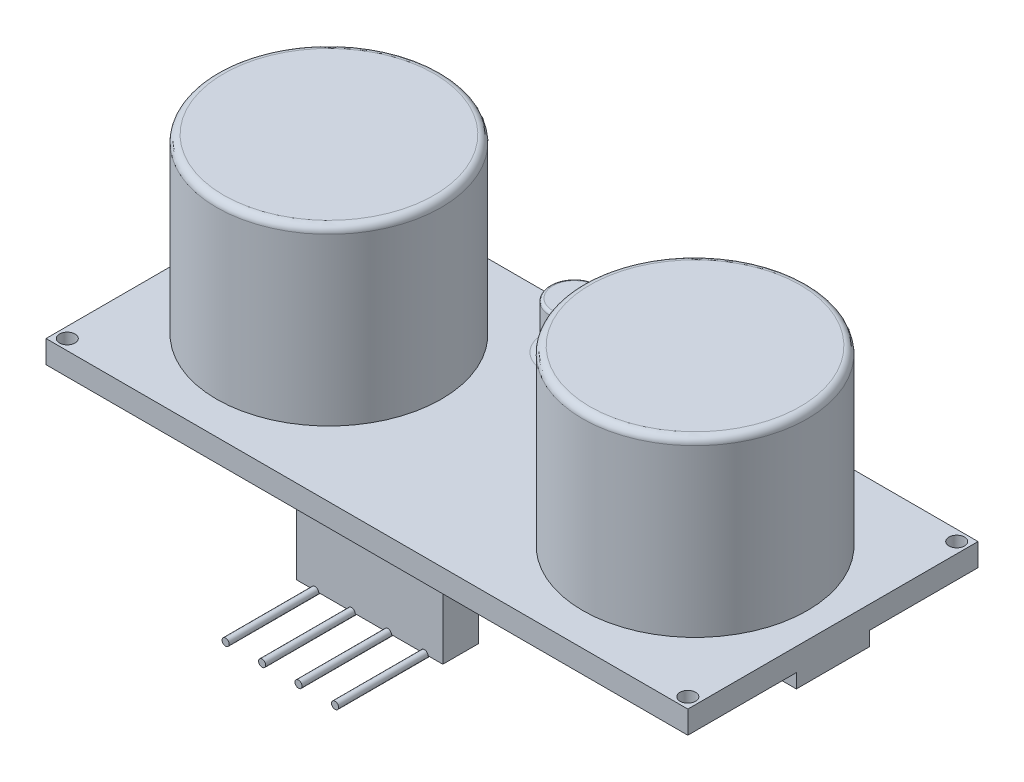
SolidWorks part; units mm, degrees
ref_plane "Front Plane" through (0, 0, 0) normal (0, 0, 1) x (1, 0, 0)
ref_plane "Top Plane" through (0, 0, 0) normal (0, 1, 0) x (1, 0, 0)
ref_plane "Right Plane" through (0, 0, 0) normal (1, 0, 0) x (0, 0, -1)
sketch "Sketch1" plane through (0, 0, 0) normal (0, 1, 0) x (1, 0, 0)
  line L1 (0, 0) -> (-45.23, 0)
  line L2 (0, 0) -> (0, 20.45)
  line L3 (0, 20.45) -> (-45.23, 20.45)
  line L4 (-45.23, 0) -> (-45.23, 20.45)
  dimension "D1" = 45.23
  dimension "D2" = 20.45
extrude "Boss-Extrude1" add sketch "Sketch1" along normal blind 1.6
sketch "Sketch2" plane through (0, 1.6, 0) normal (0, 1, 0) x (1, 0, 0)
  line L0 (-22.615, 20.45) -> (-22.615, -5.5793) construction
  line L2 (0, 20.45) -> (-45.23, 20.45) construction
  line L3 (-45.23, 10.225) -> (4.5175, 10.225) construction
  line L4 (-45.23, 20.45) -> (-45.23, 0) construction
  circle A0 centre (-35.515, 10.225) radius 7.92
  circle A1 centre (-9.715, 10.225) radius 7.92
  point P12 (-27.595, 10.225)
  point P13 (-17.635, 10.225)
  dimension "D1" = 15.84
  dimension "D2" = 9.96
  dimension "D3" = 4.98
extrude "Boss-Extrude2" add sketch "Sketch2" along normal blind 12.2
sketch "Sketch3" plane through (0, 1.6, 0) normal (0, 1, 0) x (1, 0, 0)
  line L0 (-22.615, 20.45) -> (-22.615, -3.9913) construction
  line L1 (0, 20.45) -> (-45.23, 20.45) construction
  line L2 (-25.77, 17.78) -> (-19.46, 17.78) construction
  line L3 (-25.77, 19.5) -> (-19.46, 19.5)
  line L4 (-25.77, 16.06) -> (-19.46, 16.06)
  line L5 (-45.23, 0) -> (0, 0) construction
  arc A0 (-25.77, 19.5) -> (-25.77, 16.06) centre (-25.77, 17.78) ccw
  arc A1 (-19.46, 16.06) -> (-19.46, 19.5) centre (-19.46, 17.78) ccw
  point P6 (-22.615, 17.78)
  point P11 (-27.49, 17.78)
  point P12 (-17.74, 17.78)
  dimension "D2" = 9.75
  dimension "D1" = 3.44
  dimension "D3" = 19.5
extrude "Boss-Extrude3" add sketch "Sketch3" along normal blind 3.3
sketch "Sketch4" plane through (0, 0, 0) normal (0, -1, 0) x (1, 0, 0)
  line L0 (-45.23, -10.225) -> (7.4786, -10.225) construction
  line L1 (-45.23, -20.45) -> (-45.23, 0) construction
  line L2 (0, 0) -> (0, -20.45) construction
  line L3 (-45.23, 0) -> (0, 0) construction
  line L4 (-22.615, 0) -> (-22.615, -23.6879) construction
  line L5 (-42.73, -15.275) -> (-38.73, -15.275)
  line L6 (-42.73, -15.275) -> (-42.73, -5.175)
  line L7 (-42.73, -5.175) -> (-38.73, -5.175)
  line L8 (-38.73, -15.275) -> (-38.73, -5.175)
  line L9 (-42.73, -15.275) -> (-38.73, -5.175) construction
  line L10 (-42.73, -5.175) -> (-38.73, -15.275) construction
  line L11 (-18.275, -12.8) -> (-26.955, -12.8)
  line L12 (-18.275, -12.8) -> (-18.275, -7.65)
  line L13 (-18.275, -7.65) -> (-26.955, -7.65)
  line L14 (-26.955, -12.8) -> (-26.955, -7.65)
  line L15 (-18.275, -12.8) -> (-26.955, -7.65) construction
  line L16 (-18.275, -7.65) -> (-26.955, -12.8) construction
  line L17 (0, -12.8) -> (-8.68, -12.8)
  line L18 (0, -12.8) -> (0, -7.65)
  line L19 (0, -7.65) -> (-8.68, -7.65)
  line L20 (-8.68, -12.8) -> (-8.68, -7.65)
  line L21 (0, -12.8) -> (-8.68, -7.65) construction
  line L22 (0, -7.65) -> (-8.68, -12.8) construction
  line L23 (-17.465, -0.2) -> (-27.765, -0.2)
  line L24 (-17.465, -0.2) -> (-17.465, -2.73)
  line L25 (-17.465, -2.73) -> (-27.765, -2.73)
  line L26 (-27.765, -0.2) -> (-27.765, -2.73)
  line L27 (-17.465, -0.2) -> (-27.765, -2.73) construction
  line L28 (-17.465, -2.73) -> (-27.765, -0.2) construction
  point P7 (-40.73, -10.225)
  point P13 (-22.615, -10.225)
  point P18 (-4.34, -10.225)
  point P23 (-22.615, -1.465)
  point P28 (-17.465, -1.465)
  point P29 (-27.765, -1.465)
  point P32 (0, 0)
  dimension "D1" = 10.3
  dimension "D2" = 2.53
  dimension "D3" = 0.2
  dimension "D4" = 5.15
  dimension "D5" = 8.68
  dimension "D6" = 0
  dimension "D7" = 8.68
  dimension "D8" = 5.15
  dimension "D9" = 10.1
  dimension "D10" = 4
  dimension "D11" = 6.5
extrude "Boss-Extrude4" add sketch "Sketch4" along normal blind 1
sketch "Sketch5" plane through (0, -1, 0) normal (0, -1, 0) x (1, 0, 0)
  line L8 (-27.765, -0.2) -> (-27.765, -2.73)
  line L9 (-27.765, -2.73) -> (-17.465, -2.73)
  line L10 (-17.465, -2.73) -> (-17.465, -0.2)
  line L11 (-17.465, -0.2) -> (-27.765, -0.2)
  line L12 (-27.765, -0.2) -> (-27.765, -2.73)
  line L13 (-27.765, -2.73) -> (-17.465, -2.73)
  line L14 (-17.465, -2.73) -> (-17.465, -0.2)
  line L15 (-17.465, -0.2) -> (-27.765, -0.2)
  dimension "D1" = 0
extrude "Boss-Extrude5" add sketch "Sketch5" along normal blind 3.5
sketch "Sketch6" plane through (0, 0, -0.2) normal (0, 0, 1) x (1, 0, 0)
  line L0 (-22.615, -4.5) -> (-22.615, 0) construction
  line L1 (-17.465, -4.5) -> (-27.765, -4.5) construction
  line L2 (-17.465, 0) -> (-27.765, 0) construction
  line L3 (-22.615, 0) -> (-17.465, -2.25) construction
  line L4 (-17.465, -4.5) -> (-17.465, 0) construction
  line L5 (-17.465, -2.25) -> (-27.765, -2.25) construction
  line L6 (-27.765, -4.5) -> (-27.765, 0) construction
  line L7 (-22.615, 0) -> (-17.465, -4.5) construction
  line L8 (-20.053, -2.25) -> (-22.615, -4.5) construction
  line L9 (-22.615, -4.5) -> (-21.334, -4.5) construction
  line L10 (-21.334, -4.5) -> (-21.334, 0) construction
  line L11 (-45.23, 0) -> (0, 0) construction
  line L12 (-17.465, -4.5) -> (-20.053, -2.25) construction
  line L13 (-20.053, -2.25) -> (-20.053, -4.5) construction
  line L14 (-20.053, -4.5) -> (-17.465, -2.25) construction
  line L15 (-17.465, -2.25) -> (-18.759, -2.25) construction
  line L16 (-18.759, -2.25) -> (-18.759, -4.5) construction
  circle A0 centre (-21.334, -4.5) radius 0.25
  circle A1 centre (-18.759, -4.5) radius 0.25
  circle A2 centre (-23.896, -4.5) radius 0.25
  circle A3 centre (-26.471, -4.5) radius 0.25
extrude "Boss-Extrude6" add sketch "Sketch6" along normal blind 6.3
fillet "Fillet1" radius 0.5 4 edges at (-26.471, -4.5, -0.2) (-23.896, -4.5, -0.2) (-21.334, -4.5, -0.2) (-18.759, -4.5, -0.2)
fillet "Fillet2" radius 0.5 2 edges at (-9.715, 13.8, -2.305) (-35.515, 13.8, -2.305)
fillet "Fillet3" radius 0.2 4 edges at (-17.74, 4.9, -17.78) (-22.615, 4.9, -16.06) (-27.49, 4.9, -17.78) (-22.615, 4.9, -19.5)
fillet "Fillet4" radius 0.5 4 edges at (-17.74, 1.6, -17.78) (-22.615, 1.6, -16.06) (-27.49, 1.6, -17.78) (-22.615, 1.6, -19.5)
sketch "Sketch7" plane through (0, 1.6, 0) normal (0, 1, 0) x (1, 0, 0)
  line L0 (0, 20.45) -> (-45.23, 20.45) construction
  line L2 (-45.23, 20.45) -> (-45.23, 0) construction
  line L3 (-45.23, 0) -> (0, 0) construction
  line L4 (0, 0) -> (0, 20.45) construction
  circle A0 centre (-44.48, 19.7) radius 0.55
  circle A1 centre (-44.48, 0.75) radius 0.55
  circle A2 centre (-0.75, 0.75) radius 0.55
  circle A3 centre (-0.75, 19.7) radius 0.55
  point P8 (0, 0)
  point P11 (0, 0)
  point P13 (-45.23, 18.9163)
  point P14 (-42.6545, 23.5991)
  point P16 (0, 0)
  dimension "D1" = 0.75
  dimension "D2" = 0.75
  dimension "D3" = 0.75
  dimension "D4" = 0.75
  dimension "D5" = 0.75
  dimension "D6" = 0.75
  dimension "D7" = 0.75
  dimension "D8" = 0.75
extrude "Cut-Extrude1" cut sketch "Sketch7" against normal blind 6.3
